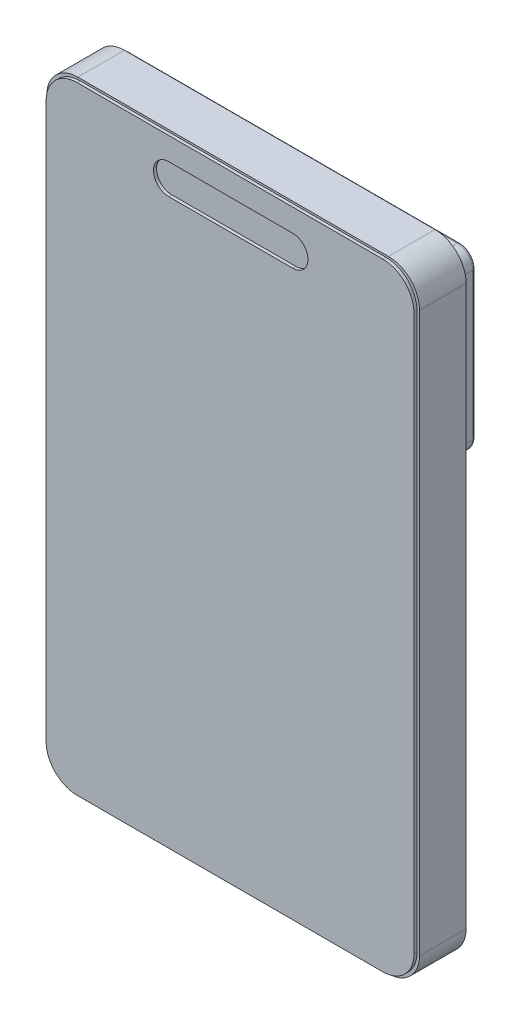
SolidWorks part; units mm, degrees
ref_plane "Front Plane" through (0, 0, 0) normal (0, 0, 1) x (1, 0, 0)
ref_plane "Top Plane" through (0, 0, 0) normal (0, 1, 0) x (1, 0, 0)
ref_plane "Right Plane" through (0, 0, 0) normal (1, 0, 0) x (0, 0, -1)
sketch "Sketch1" plane through (0, 0, 0) normal (0, 0, 1) x (1, 0, 0)
  line L1 (-60, 100) -> (60, 100)
  line L2 (-60, 100) -> (-60, -100)
  line L3 (-60, -100) -> (60, -100)
  line L4 (60, 100) -> (60, -100)
  line L5 (-60, 100) -> (60, -100) construction
  line L6 (-60, -100) -> (60, 100) construction
  point P0 (0, 0)
  dimension "D1" = 200
  dimension "D2" = 120
extrude "Boss-Extrude2" add sketch "Sketch1" along normal blind 15
fillet "Fillet2" radius 10 4 edges at (60, -100, 7.5) (-60, -100, 7.5) (-60, 100, 7.5) (60, 100, 7.5)
sketch "Sketch3" plane through (0, 0, 0) normal (0, 0, 1) x (1, 0, 0)
  line L0 (0, 100) -> (0, -100) construction
  line L1 (50, 100) -> (-50, 100) construction
  line L2 (-50, -100) -> (50, -100) construction
  line L3 (0, 68.7121) -> (-60, 68.7121) construction
  line L4 (-60, 90) -> (-60, -90) construction
  line L5 (-60, 68.7121) -> (60, 68.7121) construction
  line L6 (60, -90) -> (60, 90) construction
  line L8 (-54.9987, 95.6835) -> (54.9987, 95.6835)
  line L9 (-54.9987, 95.6835) -> (-54.9987, 41.7407)
  line L10 (-54.9987, 41.7407) -> (54.9987, 41.7407)
  line L11 (54.9987, 95.6835) -> (54.9987, 41.7407)
  line L12 (-54.9987, 95.6835) -> (54.9987, 41.7407) construction
  line L13 (-54.9987, 41.7407) -> (54.9987, 95.6835) construction
extrude "Boss-Extrude3" add sketch "Sketch3" against normal blind 5
fillet "Fillet5" radius 3.3 4 edges at (54.9987, 68.7121, -5) (0, 95.6835, -5) (-54.9987, 68.7121, -5) (0, 41.7407, -5)
fillet "Fillet6" radius 3.3 3 edges at (-54.9987, 68.7121, 0) (0, 41.7407, 0) (54.9987, 68.7121, 0)
sketch "Sketch4" plane through (0, 0, -5) normal (0, 0, -1) x (-1, 0, 0)
  circle A0 centre (-20.9407, 68.7121) radius 7.6647
  circle A1 centre (-40.7603, 58.8254) radius 7.6565
  circle A2 centre (-40.7603, 80.2258) radius 7.6565
extrude "Boss-Extrude4" add sketch "Sketch4" along normal blind 4
sketch "Sketch5" plane through (0, 0, -5) normal (0, 0, -1) x (-1, 0, 0)
  line L0 (-40.2447, 79.8965) -> (-41.6832, 79.8965) construction
  line L1 (-41.6832, 79.8965) -> (44.6267, 79.8965) construction
  line L2 (44.6267, 79.8965) -> (44.6267, 57.4799) construction
  circle A0 centre (44.6267, 79.8965) radius 3.7622
  circle A1 centre (44.6267, 57.4799) radius 3.7546
extrude "Cut-Extrude1" cut sketch "Sketch5" against normal blind 2 contours A0 | A1
sketch "Sketch6" plane through (0, 0, 0) normal (0, 0, -1) x (-1, 0, 0)
  line L1 (-54.1698, 26.9328) -> (53.8655, 26.9328)
  line L2 (-54.1698, 26.9328) -> (-54.1698, -103.014)
  line L3 (-54.1698, -103.014) -> (53.8655, -103.014)
  line L4 (53.8655, 26.9328) -> (53.8655, -103.014)
extrude "Cut-Extrude2" cut sketch "Sketch6" against normal blind 1.5
fillet "Fillet7" radius 5 2 edges at (54.1698, 26.9328, 0.75) (-53.8655, 26.9328, 0.75)
sketch "Sketch7" plane through (0, 0, 15) normal (0, 0, 1) x (1, 0, 0)
  line L1 (-59.2161, 99.3621) -> (59.2161, 99.3621)
  line L2 (-59.2161, 99.3621) -> (-59.2161, -99.3621)
  line L3 (-59.2161, -99.3621) -> (59.2161, -99.3621)
  line L4 (59.2161, 99.3621) -> (59.2161, -99.3621)
  line L5 (-59.2161, 99.3621) -> (59.2161, -99.3621) construction
  line L6 (-59.2161, -99.3621) -> (59.2161, 99.3621) construction
  point P0 (0, 0)
extrude "Boss-Extrude5" add sketch "Sketch7" along normal blind 1
fillet "Fillet8" radius 10 1 edges at (-59.2161, 99.3621, 15.5)
fillet "Fillet9" radius 10 1 edges at (59.2161, 99.3621, 15.5)
fillet "Fillet10" radius 10 2 edges at (-59.2161, -99.3621, 15.5) (59.2161, -99.3621, 15.5)
sketch "Sketch8" plane through (0, 0, 16) normal (0, 0, 1) x (1, 0, 0)
  line L1 (-19.7811, 92.0583) -> (20.2189, 92.0583)
  line L2 (-19.7811, 82.3199) -> (20.2189, 82.3199)
  arc A0 (-19.7811, 92.0583) -> (-19.7811, 82.3199) centre (-19.7811, 87.1891) ccw
  arc A1 (20.2189, 82.3199) -> (20.2189, 92.0583) centre (20.2189, 87.1891) ccw
  point P2 (0.2189, 87.1891)
extrude "Cut-Extrude3" cut sketch "Sketch8" against normal blind 1
sketch "Sketch11" plane through (0, -100, 0) normal (0, -1, 0) x (1, 0, 0)
  line L0 (-5.5176, 8.7074) -> (13.4491, 8.7074) construction
  line L1 (-5.5176, 12.3283) -> (13.4491, 12.3283)
  line L2 (-5.5176, 5.0865) -> (13.4491, 5.0865)
  arc A0 (-5.5176, 12.3283) -> (-5.5176, 5.0865) centre (-5.5176, 8.7074) ccw
  arc A1 (13.4491, 5.0865) -> (13.4491, 12.3283) centre (13.4491, 8.7074) ccw
  point P2 (3.9657, 8.7074)
extrude "Cut-Extrude4" cut sketch "Sketch11" against normal blind 11
sketch "Sketch12" plane through (0, 0, -5) normal (0, 0, -1) x (-1, 0, 0)
  line L1 (-58.1019, 95.6835) -> (58.1019, 95.6835)
  line L2 (-58.1019, 95.6835) -> (-58.1019, 38.6376)
  line L3 (-58.1019, 38.6376) -> (58.1019, 38.6376)
  line L4 (58.1019, 95.6835) -> (58.1019, 38.6376)
extrude "Boss-Extrude7" add sketch "Sketch12" against normal blind 5
fillet "Fillet11" radius 5 4 edges at (58.1019, 95.6835, -2.5) (-58.1019, 95.6835, -2.5) (58.1019, 38.6376, -2.5) (-58.1019, 38.6376, -2.5)
sketch "Sketch13" plane through (0, 0, -5) normal (0, 0, -1) x (-1, 0, 0)
  circle A0 centre (47.591, 82.4479) radius 4.5681
  circle A1 centre (47.591, 52.6031) radius 6.0296
extrude "Boss-Extrude8" add sketch "Sketch13" along normal blind 2
fillet "Fillet12" radius 1 8 edges at (56.6374, 94.2191, -5) (0, 95.6835, -5) (-56.6374, 94.2191, -5) (-58.1019, 67.1606, -5) (-56.6374, 40.1021, -5) (0, 38.6376, -5) (56.6374, 40.1021, -5) (58.1019, 67.1606, -5)
sketch "Sketch16" plane through (0, 0, 1.5) normal (0, 0, -1) x (-1, 0, 0)
  line L1 (-54.1698, 33.6279) -> (53.8655, 33.6279)
  line L2 (-54.1698, 33.6279) -> (-54.1698, -103.927)
  line L3 (-54.1698, -103.927) -> (53.8655, -103.927)
  line L4 (53.8655, 33.6279) -> (53.8655, -103.927)
extrude "Cut-Extrude5" cut sketch "Sketch16" against normal blind 1
sketch "Sketch17" plane through (0, 0, 0) normal (0, 0, -1) x (-1, 0, 0)
  line L1 (-54.541, 34.5514) -> (53.8655, 34.5514)
  line L2 (-54.541, 34.5514) -> (-54.541, -105.4486)
  line L3 (-54.541, -105.4486) -> (53.8655, -105.4486)
  line L4 (53.8655, 34.5514) -> (53.8655, -105.4486)
  dimension "D1" = 140
extrude "Cut-Extrude6" cut sketch "Sketch17" against normal blind 1.5
fillet "Fillet13" radius 4 3 edges at (54.541, 34.5514, 0.75) (54.1698, 33.6279, 2) (-53.8655, 34.5514, 0.75)
sketch "Sketch19" plane through (0, 0, 2.5) normal (0, 0, -1) x (-1, 0, 0)
  line L1 (0, -44.2793) -> (15.8132, -35.1495)
  line L2 (15.8132, -35.1495) -> (15.8132, -16.89)
  line L3 (15.8132, -16.89) -> (0, -7.7603)
  line L4 (0, -7.7603) -> (-15.8132, -16.89)
  line L5 (-15.8132, -16.89) -> (-15.8132, -35.1495)
  line L6 (-15.8132, -35.1495) -> (0, -44.2793)
extrude "Boss-Extrude9" add sketch "Sketch19" along normal blind 1.5
